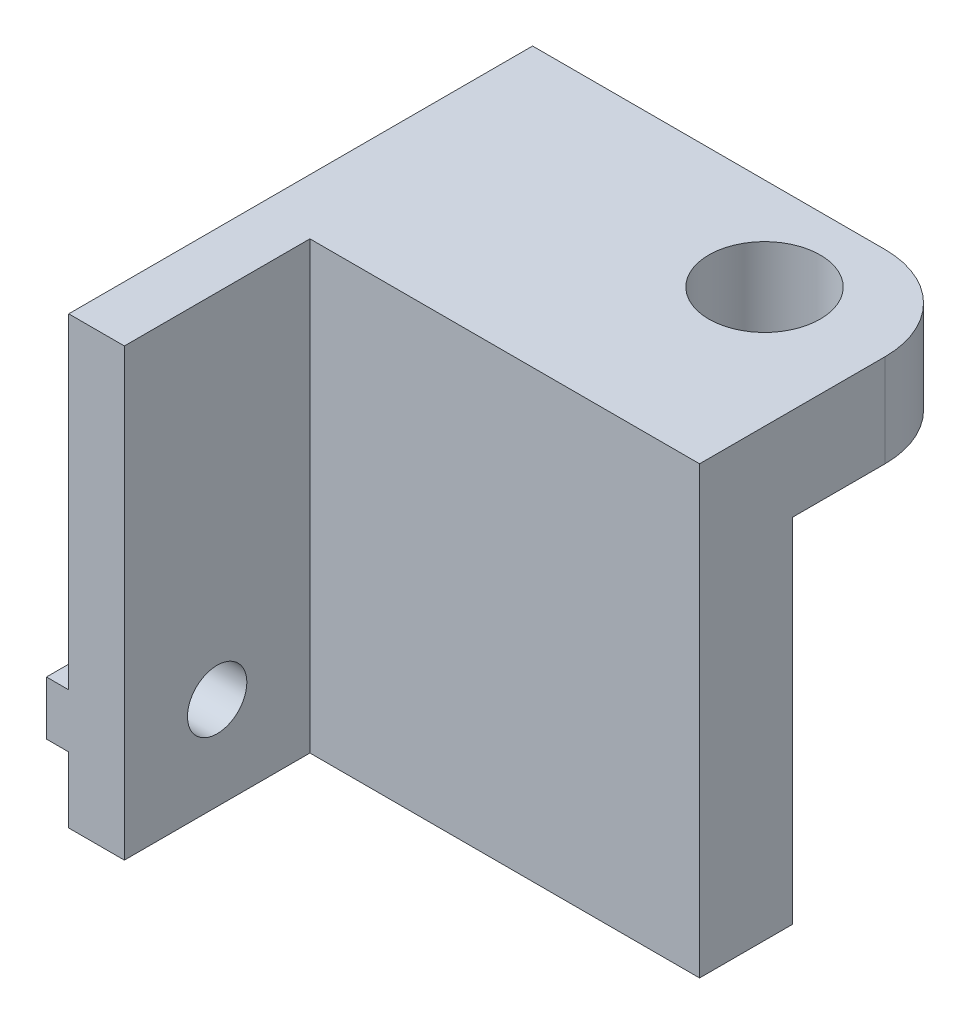
SolidWorks part; units mm, degrees
ref_plane "Front Plane" through (0, 0, 0) normal (0, 0, 1) x (1, 0, 0)
ref_plane "Top Plane" through (0, 0, 0) normal (0, 1, 0) x (1, 0, 0)
ref_plane "Right Plane" through (0, 0, 0) normal (1, 0, 0) x (0, 0, -1)
sketch "Esquisse1" plane through (0, 0, 0) normal (0, 0, 1) x (1, 0, 0)
  line L0 (-12, -5) -> (12, -5)
  line L1 (12, -5) -> (12, -1.45)
  line L2 (12, -1.45) -> (13.2, -1.45)
  line L3 (13.2, -1.45) -> (13.2, 1.45)
  line L4 (13.2, 1.45) -> (12, 1.45)
  line L5 (12, 1.45) -> (12, 19)
  line L6 (12, 19) -> (-12, 19)
  line L7 (-12, 19) -> (-12, -5)
  point P0 (13.2, 0)
  point P11 (0, -5)
  dimension "D1" = 2.9
  dimension "D2" = 1.2
  dimension "D3" = 24
  dimension "D4" = 24
  dimension "D5" = 3.55
extrude "Boss.-Extru.1" add sketch "Esquisse1" along normal blind 25
ref_plane "Plan1" through (9, 0, 0) normal (1, 0, 0) x (0, 0, -1)
sketch "Esquisse2" plane through (9, 0, 0) normal (1, 0, 0) x (0, 0, -1)
  line L0 (0, 1.45) -> (0, 19) construction
  line L1 (-10, 14) -> (0, 14)
  line L2 (-10, 14) -> (-10, 5)
  line L3 (-10, 5) -> (0, 5)
  line L4 (0, 14) -> (0, 5)
  line L5 (-25, 19) -> (0, 19) construction
  line L7 (-25, -5) -> (0, -5) construction
  dimension "D1" = 5
  dimension "D2" = 10
  dimension "D3" = 10
extrude "Enlèv. mat.-Extru.1" cut sketch "Esquisse2" against normal through all
sketch "Esquisse3" plane through (0, 0, 0) normal (0, 0, -1) x (-1, 0, 0)
  line L0 (12, 5) -> (-9, 5) construction
  line L1 (12, 5) -> (-9, 5)
  line L2 (12, 5) -> (12, -5)
  line L3 (12, -5) -> (-9, -5)
  line L4 (-9, 5) -> (-9, -5)
  line L5 (12, 5) -> (12, -5) construction
  line L6 (12, -5) -> (-12, -5) construction
  line L7 (-12, 1.45) -> (-12, 19) construction
  dimension "D1" = 3
extrude "Enlèv. mat.-Extru.2" cut sketch "Esquisse3" against normal up to surface (10 mm away) up to face at (-1.5, 9.5, 10)
sketch "Esquisse4" plane through (0, 19, 0) normal (0, 1, 0) x (1, 0, 0)
  line L0 (12, -25) -> (12, 0) construction
  line L1 (12, 0) -> (-12, 0) construction
  circle A0 centre (-5.5, -5) radius 3
  dimension "D1" = 6
  dimension "D2" = 17.5
  dimension "D3" = 5
extrude "Enlèv. mat.-Extru.3" cut sketch "Esquisse4" against normal through all and the other way through all
sketch "Esquisse5" plane through (13.2, 0, 0) normal (1, 0, 0) x (0, 0, -1)
  line L0 (0, -1.45) -> (0, 1.45) construction
  circle A0 centre (-20, 0) radius 1.6
  point P4 (0, 0)
  dimension "D1" = 3.2
  dimension "D2" = 20
extrude "MakerBeam Fixing Hole" cut sketch "Esquisse5" against normal through all
fillet "Congé2" radius 5 2 edges at (-12, 16.5, 0) (9, 14, 5)
sketch "Esquisse6" plane through (-12, 0, 0) normal (-1, 0, 0) x (0, 0, 1)
  line L0 (25, 19) -> (25, -5) construction
  line L1 (25, -5) -> (15, -5)
  line L2 (25, -5) -> (25, 19)
  line L3 (25, 19) -> (15, 19)
  line L4 (15, -5) -> (15, 19)
  line L5 (25, 19) -> (5, 19) construction
  line L6 (10, 14) -> (10, -5) construction
  line L8 (25, -5) -> (10, -5) construction
  dimension "D1" = 5
extrude "Enlèv. mat.-Extru.4" cut sketch "Esquisse6" against normal up to surface (21 mm away) up to plane "Plan1"
ref_plane "Plan2" through (19, 0, 0) normal (1, 0, 0) x (0, 0, -1)
mirror "Symétrie1" about plane through (19, 0, 0) normal (1, 0, 0) of bodies 106
sketch "Esquisse7" plane through (0, 19, 0) normal (0, 1, 0) x (1, 0, 0)
  line L0 (19, -9.6525) -> (19, 9.6525) construction
  line L1 (19, 0) -> (-12, 0)
  line L2 (19, 0) -> (19, -25)
  line L3 (19, -25) -> (-12, -25)
  line L4 (-12, 0) -> (-12, -25)
  line L7 (12, 0) -> (-7, 0) construction
  line L8 (-12, -15) -> (-12, -5) construction
  line L9 (12, -25) -> (9, -25) construction
extrude "Enlèv. mat.-Extru.5" cut sketch "Esquisse7" against normal through all
